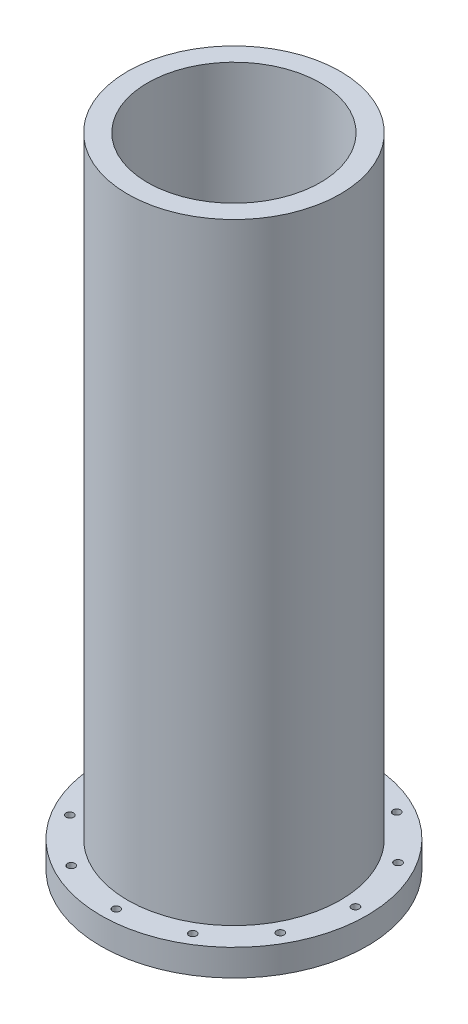
SolidWorks part; units mm, degrees
ref_plane "Front Plane" through (0, 0, 0) normal (0, 0, 1) x (1, 0, 0)
ref_plane "Top Plane" through (0, 0, 0) normal (0, 1, 0) x (1, 0, 0)
ref_plane "Right Plane" through (0, 0, 0) normal (1, 0, 0) x (0, 0, -1)
sketch "Sketch2" plane through (0, 0, 0) normal (0, 1, 0) x (1, 0, 0)
  circle A0 centre (0, 0) radius 41.275
  circle A1 centre (0, 0) radius 50.8
  dimension "D1" = 101.6
  dimension "D2" = 82.55
extrude "Boss-Extrude1" add sketch "Sketch2" along normal blind 304.8
sketch "Sketch4" plane through (0, 0, 0) normal (0, 1, 0) x (1, 0, 0)
  circle A0 centre (0, 0) radius 63.5
  circle A1 centre (0, 0) radius 44.45
  dimension "D1" = 127
extrude "Boss-Extrude3" add sketch "Sketch4" along normal blind 12.7
sketch "Sketch5" plane through (0, 12.7, 0) normal (0, 1, 0) x (1, 0, 0)
  circle A0 centre (29.354, -49.0353) radius 1.8147
  circle A1 centre (0, 0) radius 63.5 construction
  circle A2 centre (0.9037, -57.1429) radius 1.8147
  circle A3 centre (-27.7888, -49.939) radius 1.8147
  circle A4 centre (-49.0353, -29.354) radius 1.8147
  circle A5 centre (-57.1429, -0.9037) radius 1.8147
  circle A6 centre (-49.939, 27.7888) radius 1.8147
  circle A7 centre (-29.354, 49.0353) radius 1.8147
  circle A8 centre (-0.9037, 57.1429) radius 1.8147
  circle A9 centre (27.7888, 49.939) radius 1.8147
  circle A10 centre (49.0353, 29.354) radius 1.8147
  circle A11 centre (57.1429, 0.9037) radius 1.8147
  circle A12 centre (49.939, -27.7888) radius 1.8147
  point P28 (0, 0)
  dimension "D1" = 57.15
  dimension "D2" = 12
extrude "Cut-Extrude1" cut sketch "Sketch5" against normal through all both and the other way through all
